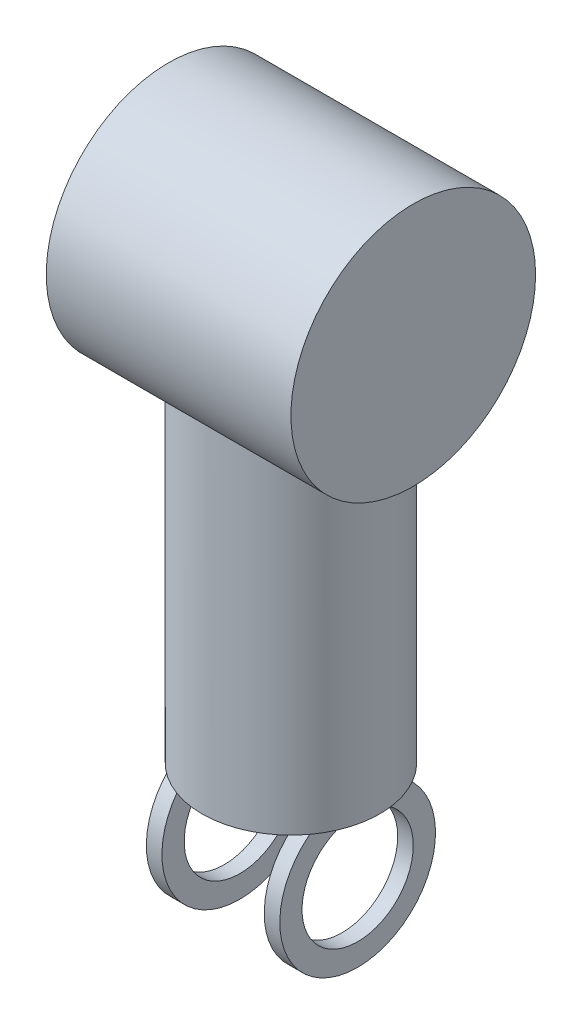
SolidWorks part; units mm, degrees
ref_plane "Front Plane" through (0, 0, 0) normal (0, 0, 1) x (1, 0, 0)
ref_plane "Top Plane" through (0, 0, 0) normal (0, 1, 0) x (1, 0, 0)
ref_plane "Right Plane" through (0, 0, 0) normal (1, 0, 0) x (0, 0, -1)
sketch "Sketch2" plane through (0, 0, 0) normal (0, 1, 0) x (1, 0, 0)
  circle A0 centre (0, 0) radius 40
  dimension "D1" = 80
extrude "Boss-Extrude2" add sketch "Sketch2" against normal blind 190
sketch "Sketch3" plane through (0, 0, 0) normal (1, 0, 0) x (0, 0, -1)
  circle A0 centre (0, 0) radius 55
  dimension "D1" = 110
extrude "Boss-Extrude3" add sketch "Sketch3" along normal mid plane 110
ref_axis "Axis1" through (0, -190, 0) along (0, 1, 0)
ref_axis "Axis2" through (0, -190, 0) along (0, 1, 0)
ref_axis "Axis3" through (0, -190, 0) along (0, 1, 0)
ref_axis "Axis4" through (55, 0, 0) along (-1, 0, 0)
ref_point "Point1"
ref_plane "Plane1" through (30, 0, 0) normal (1, 0, 0) x (0, 0, -1)
sketch "Sketch4" plane through (30, 0, 0) normal (1, 0, 0) x (0, 0, -1)
  line L0 (0, -190) -> (0, -34.5526) construction
  line L1 (-40, -190) -> (40, -190) construction
  line L2 (-18.3959, -190) -> (18.3959, -190)
  arc A0 (-18.3959, -190) -> (18.3959, -190) centre (0, -219.7757) ccw
  circle A1 centre (0, -219.7757) radius 25
  point P5 (0, -216.0554)
  point P8 (0, -219.7757)
  dimension "D1" = 50
  dimension "D2" = 70
extrude "Boss-Extrude4" add sketch "Sketch4" against normal blind 7
mirror "Mirror1" about plane through (0, 0, 0) normal (1, 0, 0) of "Boss-Extrude4"
